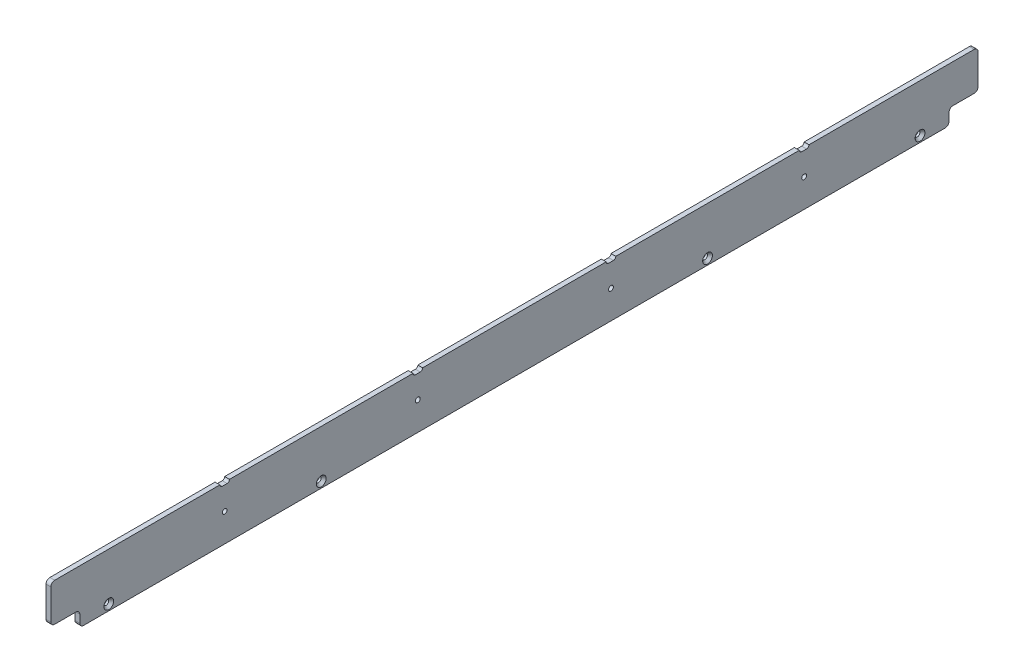
SolidWorks part; units mm, degrees
material "PC High Viscosity"
ref_plane "Front Plane" through (0, 0, 0) normal (0, 0, 1) x (1, 0, 0)
ref_plane "Top Plane" through (0, 0, 0) normal (0, 1, 0) x (1, 0, 0)
ref_plane "Right Plane" through (0, 0, 0) normal (1, 0, 0) x (0, 0, -1)
sketch "Sketch1" plane through (0, 0, 0) normal (1, 0, 0) x (0, 0, -1)
  line L1 (-609.6, 0) -> (609.6, 0)
  line L2 (-609.6, 0) -> (-609.6, 70.485)
  line L3 (-609.6, 70.485) -> (609.6, 70.485)
  line L4 (609.6, 0) -> (609.6, 70.485)
  dimension "D1" = 1219.2
  dimension "D2" = 70.485
extrude "Boss-Extrude1" add sketch "Sketch1" along normal blind 6.35
hole_wizard "CSK for 1/4 Flat Head Machine Screw1" positions "Sketch2" profile "Sketch3" countersink size "1/4" standard "ANSI Inch" end condition through all
sketch "Sketch2" plane through (6.35, 0, 0) normal (1, 0, 0) x (0, 0, -1)
  line L0 (0, 0) -> (0, 70.485) construction
  line L1 (-609.6, 0) -> (609.6, 0) construction
  line L2 (609.6, 70.485) -> (-609.6, 70.485) construction
  line L3 (-609.6, 70.485) -> (-609.6, 0) construction
  point P0 (-533.4, 7.9375)
  point P2 (-254, 7.9375)
  point P12 (254, 7.9375)
  point P13 (533.4, 7.9375)
  dimension "D1" = 355.6
  dimension "D2" = 76.2
  dimension "D3" = 7.9375
sketch "Sketch3" plane through (6.35, 7.9375, 533.4) normal (0, 1, 0) x (0, 0, -1)
  line L0 (0, 0) -> (0, 6.35)
  line L1 (0, 6.35) -> (3.3782, 6.35)
  line L2 (3.3782, 6.35) -> (3.3782, 3.5209)
  line L3 (3.3782, 3.5209) -> (6.4389, 0)
  line L5 (6.4389, 0) -> (0, 0)
  line L6 (-3.3782, 3.5209) -> (-6.4389, 0) construction
  line L11 (0, -6.35) -> (0, 107.95) construction
  dimension "Thru Hole Dia." = 6.7564
  dimension "Thru Hole Depth" = 6.35
  dimension "Near C'Sink Dia." = 12.8778
  dimension "Near C'Sink Angle" = 82
sketch "Sketch4" plane through (6.35, 0, 0) normal (1, 0, 0) x (0, 0, -1)
  line L0 (0, 0) -> (0, 70.485) construction
  line L1 (-609.6, 0) -> (-571.5, 0)
  line L2 (-609.6, 0) -> (-609.6, 20.32)
  line L3 (-609.6, 20.32) -> (-571.5, 20.32)
  line L4 (-571.5, 0) -> (-571.5, 20.32)
  line L5 (-609.6, 0) -> (609.6, 0) construction
  line L6 (609.6, 70.485) -> (-609.6, 70.485) construction
  line L7 (571.5, 0) -> (571.5, 20.32)
  line L8 (609.6, 20.32) -> (571.5, 20.32)
  line L9 (609.6, 0) -> (609.6, 20.32)
  line L10 (609.6, 0) -> (571.5, 0)
  dimension "D1" = 38.1
  dimension "D2" = 20.32
extrude "Cut-Extrude1" cut sketch "Sketch4" against normal through all
fillet "Fillet1" radius 5.08 8 edges at (3.175, 0, 571.5) (3.175, 0, -571.5) (3.175, 20.32, -571.5) (3.175, 20.32, -609.6) (3.175, 70.485, -609.6) (3.175, 70.485, 609.6) (3.175, 20.32, 609.6) (3.175, 20.32, 571.5)
hole_wizard "1/4 (0.25) Diameter Hole1" positions "Sketch5" profile "Sketch6" hole size "1/4" standard "ANSI Inch" end condition up to next
sketch "Sketch5" plane through (6.35, 0, 0) normal (1, 0, 0) x (0, 0, -1)
  line L0 (0, 0) -> (0, 70.485) construction
  line L1 (-566.42, 0) -> (566.42, 0) construction
  line L2 (604.52, 70.485) -> (-604.52, 70.485) construction
  line L4 (-457.2, 70.485) -> (457.2, 70.485) construction
  line L5 (-457.2, 70.485) -> (-457.2, 40.005) construction
  line L6 (-457.2, 40.005) -> (457.2, 40.005) construction
  line L7 (457.2, 70.485) -> (457.2, 40.005) construction
  line L8 (-381, 37.1475) -> (-127, 37.1475) construction
  line L9 (-127, 37.1475) -> (127, 37.1475) construction
  point P0 (-381, 37.1475)
  point P2 (-127, 37.1475)
  point P16 (127, 37.1475)
  point P17 (381, 37.1475)
  dimension "D1" = 33.3375
  dimension "D2" = 914.4
  dimension "D3" = 30.48
  dimension "D4" = 76.2
sketch "Sketch6" plane through (6.35, 37.1475, 381) normal (0, 1, 0) x (0, 0, -1)
  line L0 (0, 0) -> (0, 6.35)
  line L1 (0, 6.35) -> (3.175, 6.35)
  line L2 (3.175, 6.35) -> (3.175, 0)
  line L5 (3.175, 0) -> (0, 0)
  line L11 (0, -6.35) -> (0, 107.95) construction
  dimension "Thru Hole Dia." = 6.35
  dimension "Thru Hole Depth" = 6.35
sketch "Sketch7" plane through (0, 0, 0) normal (-1, 0, 0) x (0, 0, 1)
  line L0 (457.2, 70.485) -> (-457.2, 70.485) construction
  line L1 (-387.35, 70.485) -> (-374.65, 70.485)
  line L2 (-387.35, 70.485) -> (-387.35, 67.31)
  line L3 (-387.35, 67.31) -> (-374.65, 67.31)
  line L4 (-374.65, 70.485) -> (-374.65, 67.31)
  line L5 (-381, 67.31) -> (-381, 37.1475) construction
  line L6 (-127, 67.31) -> (-127, 37.1475) construction
  line L7 (-133.35, 70.485) -> (-120.65, 70.485)
  line L8 (-133.35, 70.485) -> (-133.35, 67.31)
  line L9 (-133.35, 67.31) -> (-120.65, 67.31)
  line L10 (-120.65, 70.485) -> (-120.65, 67.31)
  line L11 (0, 0) -> (0, 70.485) construction
  line L12 (0, 0) -> (0, 70.485) construction
  line L13 (120.65, 70.485) -> (120.65, 67.31)
  line L14 (133.35, 67.31) -> (120.65, 67.31)
  line L15 (133.35, 70.485) -> (133.35, 67.31)
  line L16 (133.35, 70.485) -> (120.65, 70.485)
  line L17 (374.65, 70.485) -> (374.65, 67.31)
  line L18 (387.35, 67.31) -> (374.65, 67.31)
  line L19 (387.35, 70.485) -> (387.35, 67.31)
  line L20 (387.35, 70.485) -> (374.65, 70.485)
  dimension "D1" = 12.7
  dimension "D2" = 3.175
extrude "Cut-Extrude2" cut sketch "Sketch7" against normal through all
fillet "Fillet2" radius 3.175 8 edges at (3.175, 67.31, 374.65) (3.175, 67.31, 387.35) (3.175, 67.31, 133.35) (3.175, 67.31, 120.65) (3.175, 67.31, -133.35) (3.175, 67.31, -120.65) (3.175, 67.31, -374.65) (3.175, 67.31, -387.35)
